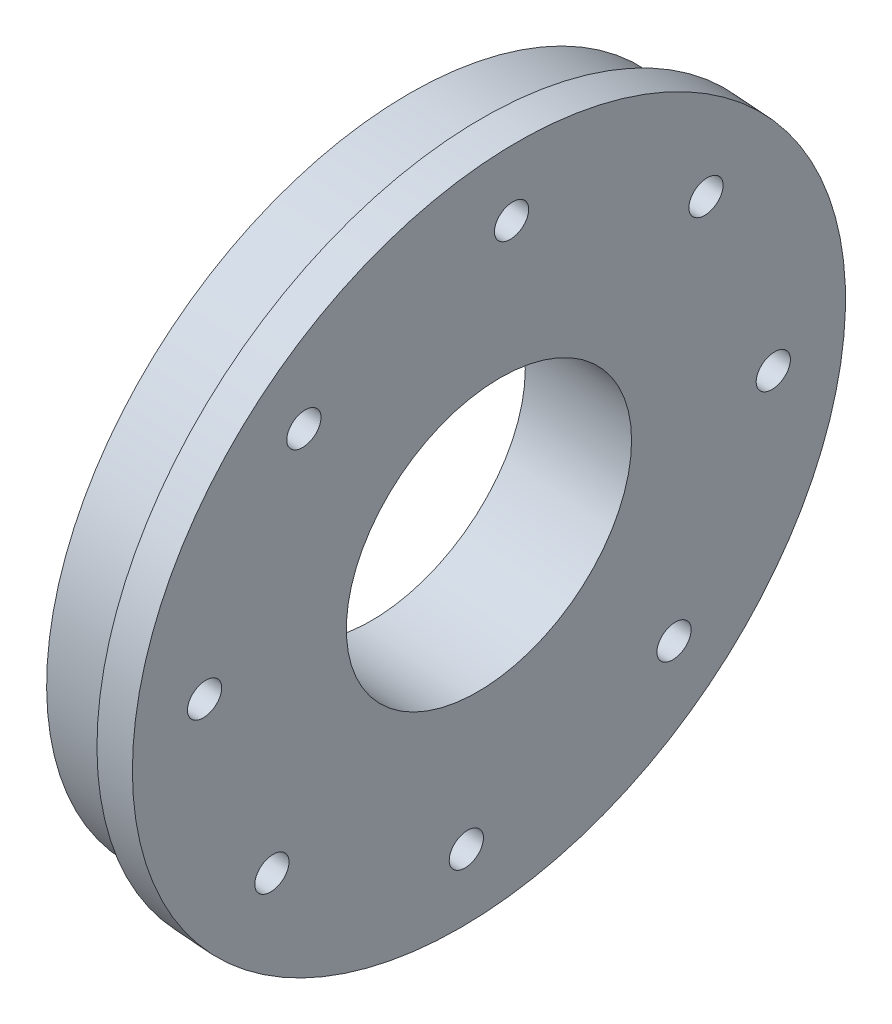
SolidWorks part; units mm, degrees
ref_plane "Front Plane" through (0, 0, 0) normal (0, 0, 1) x (1, 0, 0)
ref_plane "Top Plane" through (0, 0, 0) normal (0, 1, 0) x (1, 0, 0)
ref_plane "Right Plane" through (0, 0, 0) normal (1, 0, 0) x (0, 0, -1)
sketch "Sketch1" plane through (234.2789, -18.689, 0) normal (0.9968, -0.0795, 0) x (0, 0, -1)
  circle A1 centre (-43.1743, 8.5503) radius 14.9606
  dimension "D1" = 29.9212
extrude "Boss-Extrude1" add sketch "Sketch1" against normal blind 4.7625
sketch "Sketch2" plane through (234.2789, -18.689, 0) normal (0.9968, -0.0795, 0) x (0, 0, -1)
  circle A0 centre (-43.1743, 8.5503) radius 6.35
  dimension "D1" = 12.7
extrude "Cut-Extrude1" cut sketch "Sketch2" against normal blind 6.35
sketch "Sketch3" plane through (229.5315, -18.3103, 0) normal (-0.9968, 0.0795, 0) x (0, 0, 1)
  circle A0 centre (43.1743, 21.2503) radius 0.762
  circle A1 centre (43.1743, 8.5503) radius 14.9606 construction
  circle A2 centre (43.1743, 8.5503) radius 14.9606
  circle A3 centre (52.1545, 17.5306) radius 0.762
  circle A4 centre (55.8743, 8.5503) radius 0.762
  circle A5 centre (52.1545, -0.4299) radius 0.762
  circle A6 centre (43.1743, -4.1497) radius 0.762
  circle A7 centre (34.194, -0.4299) radius 0.762
  circle A8 centre (30.4743, 8.5503) radius 0.762
  circle A9 centre (34.194, 17.5306) radius 0.762
  point P21 (43.1743, 8.5503)
  dimension "D1" = 1.524
  dimension "D3" = 12.7
  dimension "D2" = 8
extrude "Cut-Extrude2" cut sketch "Sketch3" against normal blind 10 contours A8 | A0 | A3 | A4 | A5 | A6 | A7 | A9 region at (231.2213, 2.8727, 43.1743) region at (230.9255, -0.8352, 52.1545) region at (230.2114, -9.787, 55.8743) region at (229.4973, -18.7389, 52.1545) region at (229.2015, -22.4468, 43.1743) region at (229.4973, -18.7389, 34.194) region at (230.2114, -9.787, 30.4743)
sketch "Sketch4" plane through (234.2789, -18.689, 0) normal (0.9968, -0.0795, 0) x (0, 0, -1)
  line L0 (-58.1349, 8.5503) -> (-28.2137, 8.5503) construction
  circle A0 centre (-43.1743, 8.5503) radius 14.9606 construction
sketch "Sketch5" plane through (234.2789, -18.689, 0) normal (-0.9968, 0.0795, 0) x (0, 0, 1)
  circle A0 centre (43.1743, 8.5503) radius 14.9606 construction
  circle A1 centre (43.1743, 8.5503) radius 14.9606
  circle A2 centre (43.1743, 8.5503) radius 15.875
  dimension "D1" = 31.75
extrude "Boss-Extrude2" add sketch "Sketch5" along normal blind 1.5875
ref_axis "Axis1" through (230.2414, -9.7894, 43.1743) along (0.9968, -0.0795, 0)
ref_point "Point1"
